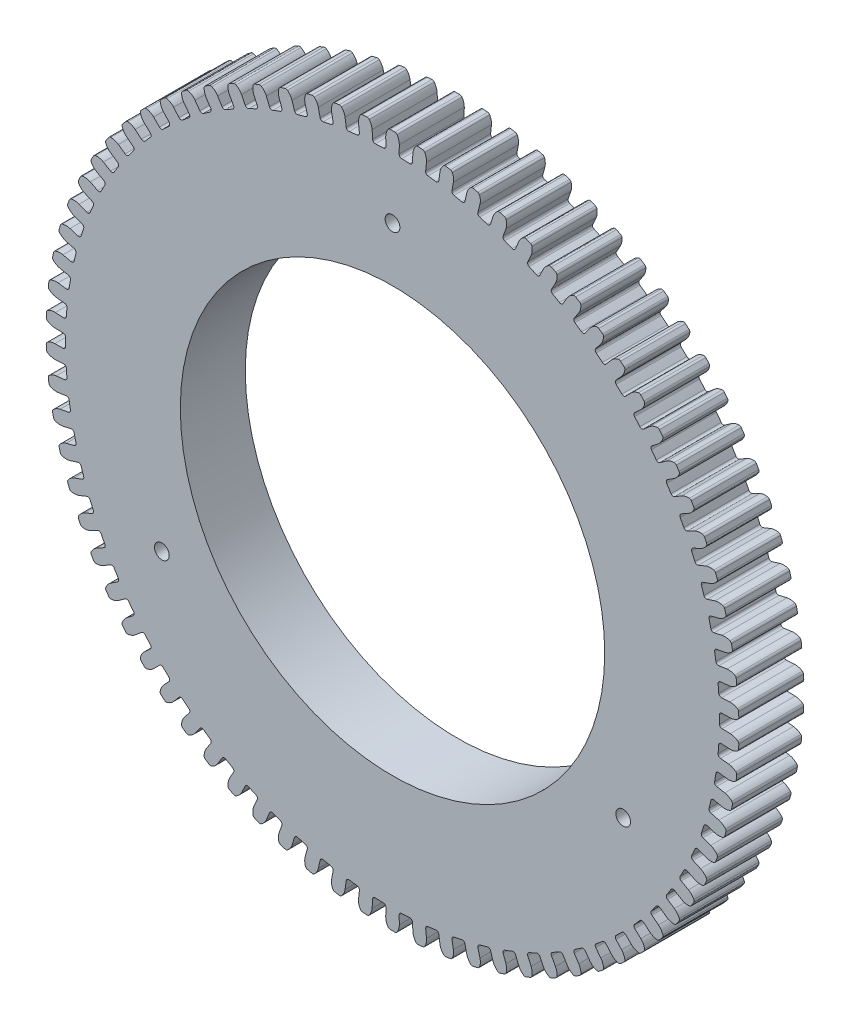
SolidWorks part; units mm, degrees
ref_plane "Front Plane" through (0, 0, 0) normal (0, 0, 1) x (1, 0, 0)
ref_plane "Top Plane" through (0, 0, 0) normal (0, 1, 0) x (1, 0, 0)
ref_plane "Right Plane" through (0, 0, 0) normal (1, 0, 0) x (0, 0, -1)
sketch "Diametros-Corona" plane through (0, 0, 0) normal (0, 0, 1) x (1, 0, 0)
  circle A12 centre (0, 0) radius 75.5 construction
  circle A19 centre (0, 0) radius 78 construction
  circle A32 centre (0, 0) radius 80 construction
  circle A33 centre (0, 0) radius 49 construction
  dimension "Di" = 151
  dimension "Dp" = 156
  dimension "De" = 160
  dimension "D2" = 98
sketch "Machote-Engrane" plane through (0, 0, 0) normal (0, 0, 1) x (1, 0, 0)
  line L0 (0, 0) -> (1.611, 79.9838)
  line L5 (0, 0) -> (0, 80) construction
  line L6 (3.2213, 79.9351) -> (0, 0) construction
  line L7 (0, 0) -> (-1.611, 79.9838)
  line L8 (0, 0) -> (4.8303, 79.854) construction
  line L9 (0, 0) -> (-3.2213, 79.9351) construction
  line L10 (0, 0) -> (-4.8303, 79.854) construction
  circle A12 centre (0, 0) radius 75.5
  circle A19 centre (0, 0) radius 78 construction
  circle A32 centre (0, 0) radius 80 construction
  circle A33 centre (0, 0) radius 49
  circle A39 centre (-1.5707, 77.9842) radius 3.1416
  circle A46 centre (-2.1323, 76.0701) radius 0.6
  circle A47 centre (-0.5411, 79.3982) radius 0.6
  circle A48 centre (0.5413, 79.3982) radius 0.6
  circle A49 centre (2.1323, 76.0701) radius 0.6
  circle A50 centre (1.5709, 77.9842) radius 3.1416
  dimension "Di" = 151
  dimension "Dp" = 156
  dimension "De" = 160
  dimension "Agujero" = 98
  dimension "Paso" = 6.2832
  dimension "Filet2 rx2" = 1.2
  dimension "Filet1 rx2" = 1.2
  dimension "Filet3 rx2" = 1.2
  dimension "Filet4 rx2" = 1.2
  dimension "D1" = 6.2832
  dimension "Ang3. (360/N)/4" = 1.154
  dimension "Ang4. (360/N)/4" = 1.154
  dimension "Ang5. (360/N)/4" = 1.154
  dimension "Ang6. (360/N)/4" = 1.154
  dimension "Ang2. (360/N)/4" = 1.154
  dimension "Ang1. (360/N)/4" = 1.154
sketch "Diente" plane through (0, 0, 0) normal (0, 0, 1) x (1, 0, 0)
  line L0 (0, 0) -> (0.9867, 48.9901)
  line L5 (0, 0) -> (0, 49) construction
  line L6 (1.973, 48.9603) -> (0, 0) construction
  line L7 (0, 0) -> (-0.9867, 48.9901)
  line L8 (0, 0) -> (2.9585, 48.9106) construction
  line L9 (0, 0) -> (-1.973, 48.9603) construction
  line L10 (0, 0) -> (-2.9585, 48.9106) construction
  line L11 (0, 79.657) -> (0, 79.6575) construction
  line L13 (-1.5324, 76.0822) -> (-1.5707, 77.9842)
  line L14 (1.5324, 76.0822) -> (1.5709, 77.994)
  circle A33 centre (0, 0) radius 49 construction
  arc A46 (-2.1154, 75.4704) -> (-1.5324, 76.0822) centre (-2.1323, 76.0701) ccw
  arc A47 (-0.5451, 79.9981) -> (-1.0396, 79.732) centre (-0.5411, 79.3982) ccw
  arc A48 (0.0001, 79.6573) -> (0, 79.657) centre (0.5413, 79.3982) ccw
  arc A49 (1.5324, 76.0822) -> (2.1154, 75.4704) centre (2.1323, 76.0701) ccw
  arc A50 (-1.0396, 79.732) -> (-1.5707, 77.9842) centre (1.5709, 77.9842) ccw
  arc A51 (0.0001, 79.6573) -> (0, 79.6575) centre (-0.5411, 79.3982) ccw
  arc A52 (0, 79.1393) -> (0.0001, 79.139) centre (0.5413, 79.3982) ccw
  arc A53 (0.5454, 79.9981) -> (-0.5451, 79.9981) centre (0, 0) ccw
  arc A54 (1.0398, 79.732) -> (0.5454, 79.9981) centre (0.5413, 79.3982) ccw
  arc A55 (0, 79.1388) -> (0.0001, 79.139) centre (-0.5411, 79.3982) ccw
  arc A56 (1.5709, 77.994) -> (1.0398, 79.732) centre (-1.5707, 77.9842) ccw
  arc A58 (2.1154, 75.4704) -> (-2.1154, 75.4704) centre (0, 0) ccw
  dimension "D1" = 6.2832
  dimension "Agujero" = 98
  dimension "Filet2 rx2" = 1.2
  dimension "Filet1 rx2" = 1.2
  dimension "Filet3 rx2" = 1.2
  dimension "Filet4 rx2" = 1.2
  dimension "Ang3. (360/N)/4" = 1.154
  dimension "Ang4. (360/N)/4" = 1.154
  dimension "Ang5. (360/N)/4" = 1.154
  dimension "Ang6. (360/N)/4" = 1.154
  dimension "Ang2. (360/N)/4" = 1.154
  dimension "Ang1. (360/N)/4" = 1.154
sketch "Extrusion-Di" plane through (0, 0, 0) normal (0, 0, 1) x (1, 0, 0)
  circle A12 centre (0, 0) radius 75.5
  circle A19 centre (0, 0) radius 78 construction
  circle A32 centre (0, 0) radius 80 construction
  circle A33 centre (0, 0) radius 49
  dimension "Di" = 151
  dimension "Dp" = 156
  dimension "De" = 160
  dimension "Agujero" = 98
extrude "Boss-Extrude1" add sketch "Extrusion-Di" along normal blind 7.5 and the other way blind 7.5
extrude "Boss-Extrude2" add sketch "Diente" along normal blind 7.5 and the other way blind 7.5 contours A56 A54 A53 A47 A50 L13 A46 A58 A49 L14
pattern_circular "CirPattern1" count 78 over 360 of "Boss-Extrude2"
sketch "Sketch6" plane through (0, 0, 7.5) normal (0, 0, 1) x (1, 0, 0)
  circle A0 centre (0, 61.5) radius 1.7
  dimension "D2" = 3.4
  dimension "D1" = 61.5
extrude "Cut-Extrude1" cut sketch "Sketch6" against normal through all both and the other way through all
pattern_circular "CirPattern2" count 3 over 360 about axis through (0, 0, 7.5) along (0, 0, 1) of "Cut-Extrude1"
equation "\"ND\"= 78'Dientes"
equation "\"PD\"= 0.5'Paso: Dientes/mm pero es 12.7 dientes/pulg"
equation "\"D\"= \"ND\" / \"PD\"'diam. paso"
equation "\"p\"= ( PI * \"D\" ) / \"ND\"'paso circular"
equation "\"m\"= 1 / \"PD\"'modulo"
equation "\"a\"= 1 / \"PD\"'addendum"
equation "\"b\"= 1.25 / \"PD\"'Pie del diente o dedendum"
equation "\"ht\"= \"a\" + \"b\"'Altura del diente"
equation "\"c\"= \"b\" - \"a\"'Claro del diete"
equation "\"t\"= PI / ( 2 * \"PD\" )'Espesor del diente"
equation "\"De\"= \"D\" + ( 2 * \"a\" )'Diam. Externo"
equation "\"Di\"= \"D\" - ( 2 * \"b\" )'Diam. Interno"
equation "\"r\"= 0.3 * \"m\"'radio de filete"
equation "\"Agujero\"=98"
equation "\"D2@Diametros-Corona\"=\"Agujero\""
equation "\"Agujero@Extrusion-Di\" = \"Agujero\""
equation "\"Di@Diametros-Corona\"=\"Di\""
equation "\"De@Diametros-Corona\"=\"De\""
equation "\"Dp@Extrusion-Di\"=\"D\""
equation "\"De@Extrusion-Di\"=\"De\""
equation "\"Di@Extrusion-Di\"=\"Di\""
equation "\"D1\"= 360 / \"ND\""
equation "\"Paso@Machote-Engrane\"= \"p\""
equation "\"Filet2 rx2@Machote-Engrane\" = \"r\" * 2"
equation "\"Filet1 rx2@Machote-Engrane\" = \"r\" * 2"
equation "\"Filet3 rx2@Machote-Engrane\" = \"r\" * 2"
equation "\"Filet4 rx2@Machote-Engrane\" = \"r\" * 2"
equation "\"Ang1. (360/N)/4@Machote-Engrane\" =  ( 360 / \"ND\" )  / 4"
equation "\"Ang2. (360/N)/4@Machote-Engrane\" =  ( 360 / \"ND\" )  / 4"
equation "\"Ang3. (360/N)/4@Machote-Engrane\" =  ( 360 / \"ND\" )  / 4"
equation "\"Ang4. (360/N)/4@Machote-Engrane\" =  ( 360 / \"ND\" )  / 4"
equation "\"Ang5. (360/N)/4@Machote-Engrane\" =  ( 360 / \"ND\" )  / 4"
equation "\"Ang6. (360/N)/4@Machote-Engrane\" =  ( 360 / \"ND\" )  / 4"
equation "\"Agujero@Machote-Engrane\"=\"Agujero\""
equation "\"Di@Machote-Engrane\"=\"Di\""
equation "\"Dp@Machote-Engrane\"=\"D\""
equation "\"De@Machote-Engrane\"=\"De\""
equation "\"D1@Sketch6\"=(((136-110)/2) + 110)/2"
